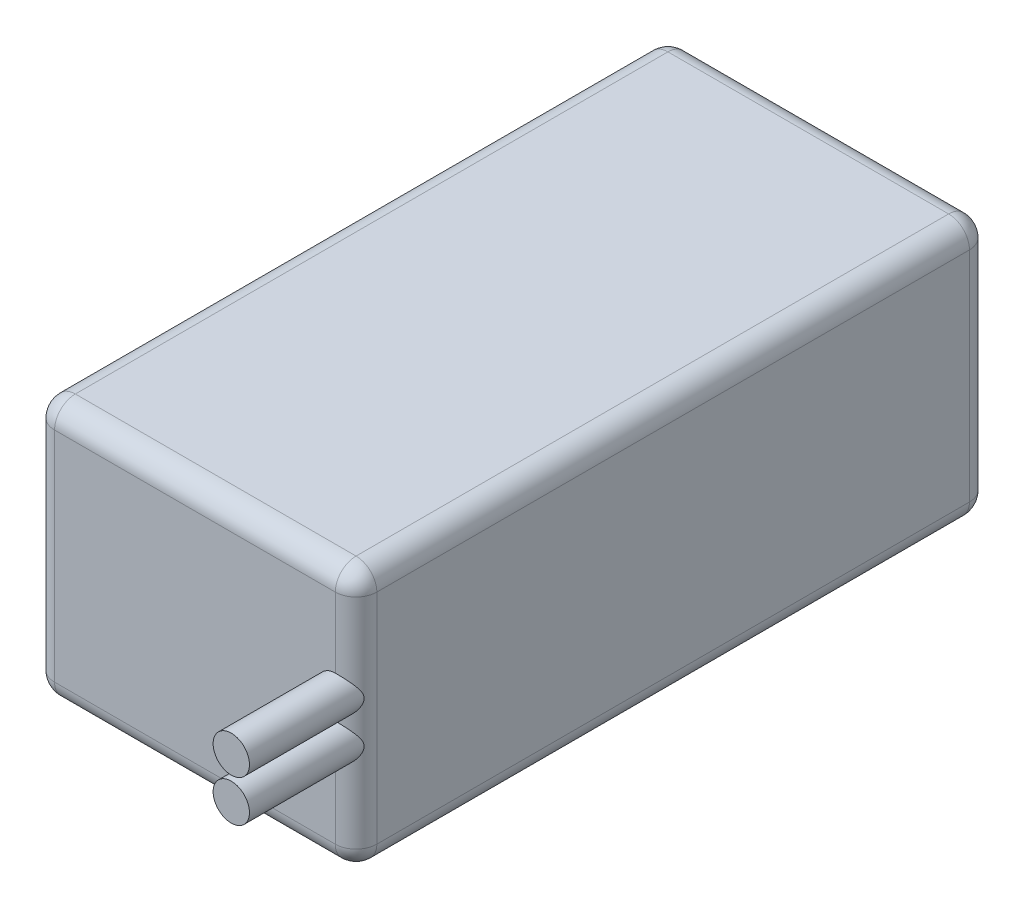
SolidWorks part; units mm, degrees
ref_plane "Front Plane" through (0, 0, 0) normal (0, 0, 1) x (1, 0, 0)
ref_plane "Top Plane" through (0, 0, 0) normal (0, 1, 0) x (1, 0, 0)
ref_plane "Right Plane" through (0, 0, 0) normal (1, 0, 0) x (0, 0, -1)
sketch "Sketch1" plane through (0, 0, 0) normal (0, 1, 0) x (1, 0, 0)
  line L1 (-15.5, 30.5) -> (15.5, 30.5)
  line L2 (-15.5, 30.5) -> (-15.5, -30.5)
  line L3 (-15.5, -30.5) -> (15.5, -30.5)
  line L4 (15.5, 30.5) -> (15.5, -30.5)
  line L5 (-15.5, 30.5) -> (15.5, -30.5) construction
  line L6 (-15.5, -30.5) -> (15.5, 30.5) construction
  point P0 (0, 0)
  dimension "D1" = 61
  dimension "D2" = 31
extrude "Boss-Extrude1" add sketch "Sketch1" along normal blind 25
sketch "Sketch2" plane through (0, 0, 30.5) normal (0, 0, 1) x (1, 0, 0)
  line L0 (-15.5, 12.5) -> (15.5, 12.5) construction
  line L1 (-15.5, 25) -> (-15.5, 0) construction
  line L2 (15.5, 25) -> (15.5, 0) construction
  line L4 (15.5, 12.5) -> (11.5, 12.5)
  line L5 (15.5, 12.5) -> (15.5, 16.5)
  line L6 (15.5, 16.5) -> (11.5, 16.5)
  line L7 (11.5, 12.5) -> (11.5, 16.5)
  line L8 (15.5, 12.5) -> (11.5, 16.5) construction
  line L9 (15.5, 16.5) -> (11.5, 12.5) construction
  circle A0 centre (13.5, 14.5) radius 1.75
  circle A1 centre (13.5, 10.5) radius 1.75
  dimension "D1" = 3.5
  dimension "D2" = 4
extrude "Boss-Extrude2" add sketch "Sketch2" along normal blind 10 contours A0 | A1 region at (13.5, 14.5, 30.5) region at (13.5, 10.5, 30.5)
fillet "Fillet1" radius 2 12 edges at (-15.5, 0, 0) (-15.5, 12.5, -30.5) (0, 0, -30.5) (15.5, 12.5, -30.5) (15.5, 0, 0) (-15.5, 12.5, 30.5) (15.5, 12.5, 30.5) (0, 0, 30.5) (0, 25, 30.5) (-15.5, 25, 0) (0, 25, -30.5) (15.5, 25, 0)
